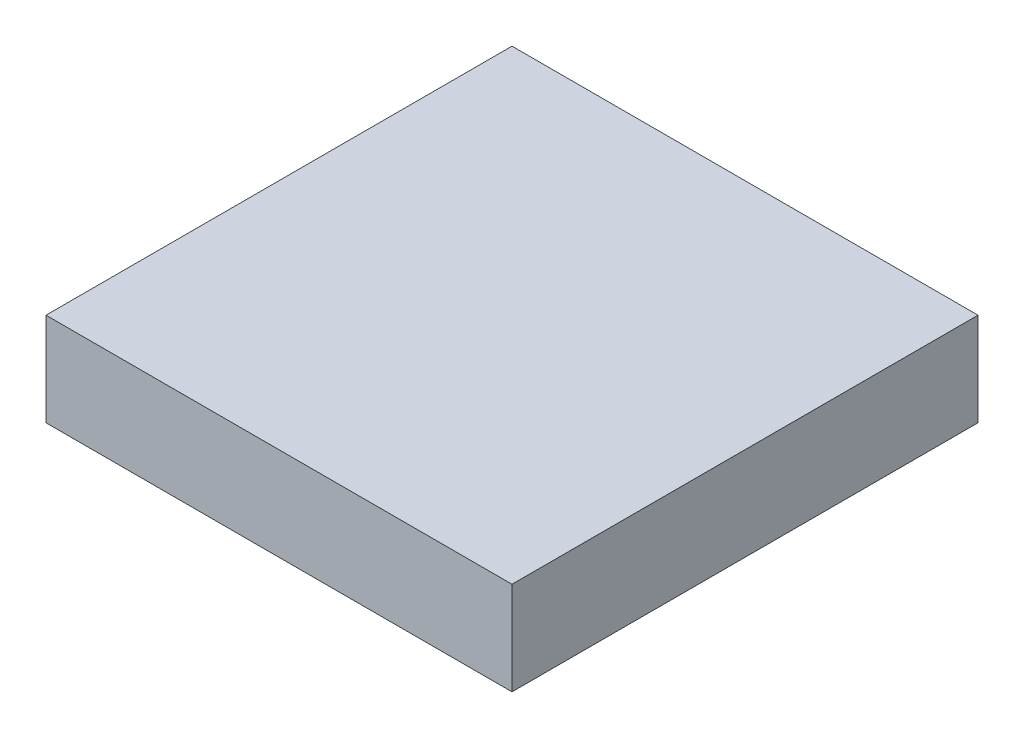
SolidWorks part; units mm, degrees
ref_plane "Front Plane" through (0, 0, 0) normal (0, 0, 1) x (1, 0, 0)
ref_plane "Top Plane" through (0, 0, 0) normal (0, 1, 0) x (1, 0, 0)
ref_plane "Right Plane" through (0, 0, 0) normal (1, 0, 0) x (0, 0, -1)
sketch "Sketch1" plane through (0, 0, 0) normal (0, 1, 0) x (1, 0, 0)
  line L0 (-2.0976, 1.7) -> (2.0976, 1.7)
  line L1 (-2.0976, -1.7) -> (2.0976, -1.7)
  line L2 (0, 1.7) -> (0, -1.7) construction
  line L4 (7.5, -7.5) -> (-7.5, -7.5)
  line L5 (7.5, -7.5) -> (7.5, 7.5)
  line L6 (7.5, 7.5) -> (-7.5, 7.5)
  line L7 (-7.5, -7.5) -> (-7.5, 7.5)
  line L8 (7.5, -7.5) -> (-7.5, 7.5) construction
  line L9 (7.5, 7.5) -> (-7.5, -7.5) construction
  circle A0 centre (0, 0) radius 2.7
  point P10 (0, 0)
  dimension "D1" = 5.4
  dimension "D2" = 3.4
  dimension "D3" = 15
  dimension "D4" = 15
extrude "Boss-Extrude1" add sketch "Sketch1" against normal blind 5 contours L7 L4 L5 L6 A0 | L0 A0 | L1 A0 region at (0, 0, -2.1071) region at (0, 0, 2.1071) region at (0, 0, 7.2879)
extrude "Boss-Extrude2" add sketch "Sketch1<3>" along normal blind 3 contours L7 L4 L5 L6 A0 | L0 A0 | L1 A0 L0 | L1 A0 region at (0, 0, -2.1071) region at (0, 0, 0) region at (0, 0, 2.1071) region at (0, 0, 7.2879)
sketch "Sketch1<3>" plane through (0, 0, 0) normal (0, 1, 0) x (1, 0, 0) same geometry as "Sketch1"
chamfer "Chamfer1" distance 5 angle 45 4 edges at (-7.5, -5, 0) (0, -5, -7.5) (7.5, -5, 0) (0, -5, 7.5)
